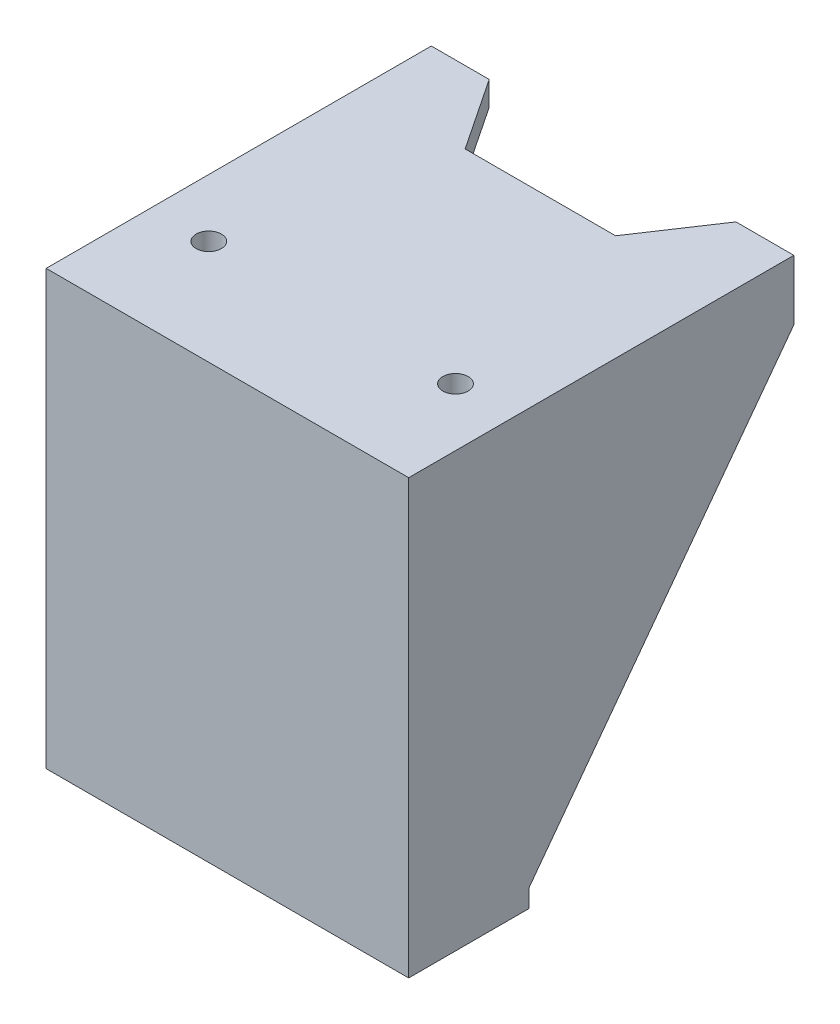
SolidWorks part; units mm, degrees
ref_plane "Front Plane" through (0, 0, 0) normal (0, 0, 1) x (1, 0, 0)
ref_plane "Top Plane" through (0, 0, 0) normal (0, 1, 0) x (1, 0, 0)
ref_plane "Right Plane" through (0, 0, 0) normal (1, 0, 0) x (0, 0, -1)
sketch "Sketch2" plane through (0, 0, 0) normal (0, 1, 0) x (1, 0, 0)
  line L0 (15.061, 0) -> (15.061, 32)
  line L1 (-12.561, 2.5) -> (12.561, 2.5)
  line L2 (-12.561, 2.5) -> (-12.561, 32)
  line L4 (12.561, 2.5) -> (12.561, 32)
  line L5 (15.061, 32) -> (12.561, 32)
  line L7 (-15.061, 32) -> (-15.061, 0)
  line L8 (-15.061, 0) -> (15.061, 0)
  line L10 (-15.061, 32) -> (-12.561, 32)
  point P4 (0, 2.5)
  point P12 (0, 0)
  dimension "D1" = 2.5
  dimension "D2" = 2.5
  dimension "D3" = 29.5
  dimension "D4" = 25.122
extrude "Boss-Extrude1" add sketch "Sketch2" along normal blind 32.5
sketch "Sketch4" plane through (0, 0, 0) normal (0, -1, 0) x (1, 0, 0)
  line L4 (-7.5, -6) -> (7.5, -6)
  line L9 (15.061, 0) -> (-15.061, 0)
  line L13 (-12.561, -2.5) -> (-12.561, -32) construction
  line L18 (-12.561, -10) -> (-7.5, -6)
  line L23 (12.561, -32) -> (12.561, -2.5) construction
  line L26 (12.561, -10) -> (7.5, -6)
  line L32 (-12.561, -10) -> (-15.061, -10)
  line L33 (-15.061, -32) -> (-15.061, 0) construction
  line L34 (-15.061, -10) -> (-15.061, 0)
  line L35 (12.561, -10) -> (15.061, -10)
  line L36 (15.061, 0) -> (15.061, -32) construction
  line L37 (15.061, -10) -> (15.061, 0)
  circle A2 centre (-10.2499, -4.95) radius 1.05
  circle A5 centre (10.2499, -4.95) radius 1.05
  point P31 (0, -6)
  dimension "D5" = 2.1
  dimension "D10" = 15
  dimension "D11" = 10
  dimension "D2" = 6
  dimension "D7" = 4.95
extrude "Boss-Extrude2" add sketch "Sketch4" along normal blind 1.5
sketch "Sketch5" plane through (0, 32.5, 0) normal (0, 1, 0) x (1, 0, 0)
  line L0 (-15.061, 32) -> (-10.2499, 32)
  line L9 (-10.2499, 32) -> (-6.25, 26)
  line L13 (-15.061, 0) -> (15.061, 0) construction
  line L14 (15.061, 0) -> (-15.061, 0)
  line L15 (-15.061, 0) -> (-15.061, 32)
  line L20 (15.061, 0) -> (15.061, 32)
  line L21 (-6.25, 26) -> (6.25, 26)
  line L22 (6.25, 26) -> (10.2499, 32)
  line L23 (10.2499, 32) -> (15.061, 32)
  circle A0 centre (-10.2499, 4.95) radius 1.05 construction
  circle A1 centre (-10.2499, 8.7) radius 1.05
  circle A2 centre (10.2499, 8.7) radius 1.05
  point P6 (0, 26)
  dimension "D4" = 0
  dimension "D1" = 8.7
  dimension "D2" = 12.5
  dimension "D3" = 20.4998
  dimension "D5" = 6
extrude "Boss-Extrude3" add sketch "Sketch5" along normal blind 2
sketch "Sketch6" plane through (-15.061, 0, 0) normal (-1, 0, 0) x (0, 0, 1)
  line L0 (-10, 0) -> (-32, 29.5)
  line L1 (-32, 29.5) -> (-32, 0)
  line L2 (-32, 0) -> (-10, 0)
  line L3 (-32, 34.5) -> (-32, 0) construction
  point P6 (-32, 34.5)
  point P7 (-32, 28.8772)
  dimension "D1" = 5
extrude "Cut-Extrude1" cut sketch "Sketch6" against normal through all
